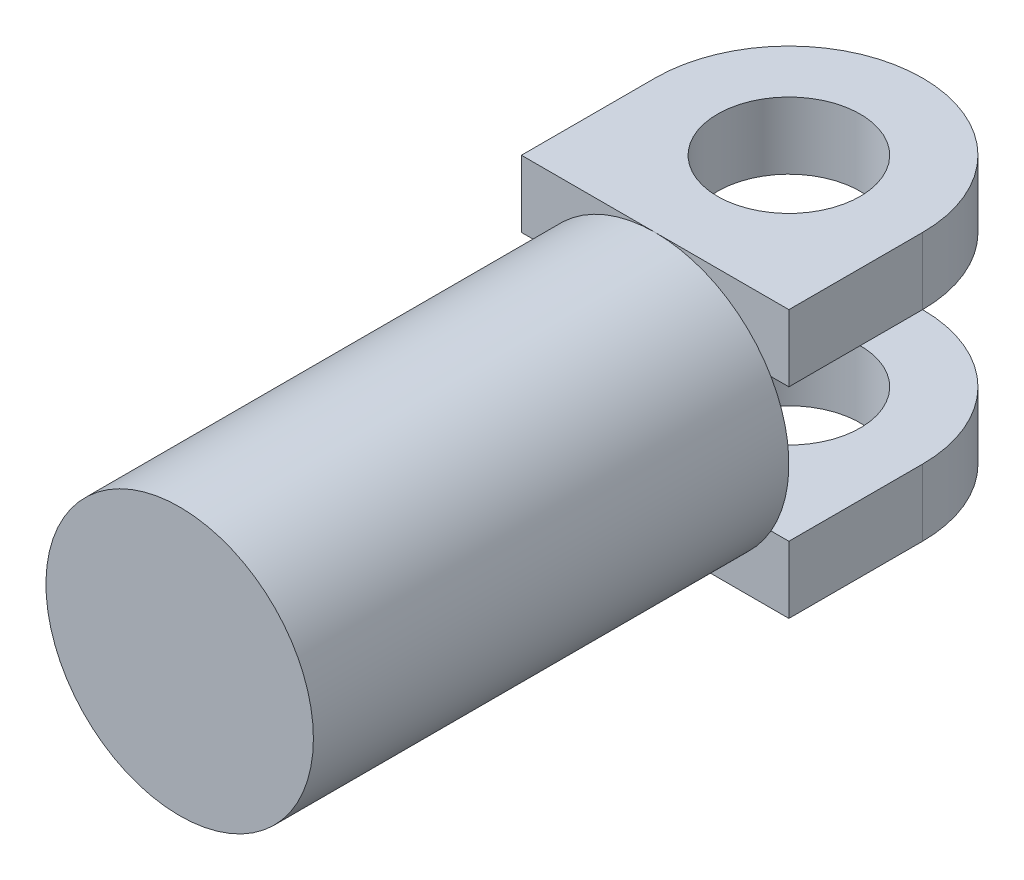
SolidWorks part; units mm, degrees
ref_plane "Front Plane" through (0, 0, 0) normal (0, 0, 1) x (1, 0, 0)
ref_plane "Top Plane" through (0, 0, 0) normal (0, 1, 0) x (1, 0, 0)
ref_plane "Right Plane" through (0, 0, 0) normal (1, 0, 0) x (0, 0, -1)
sketch "Sketch1" plane through (0, 0, 0) normal (0, 0, 1) x (1, 0, 0)
  circle A0 centre (0, 0) radius 90
  dimension "D1" = 180
extrude "Boss-Extrude1" add sketch "Sketch1" along normal blind 320
sketch "Sketch2" plane through (0, 0, 0) normal (0, 1, 0) x (1, 0, 0)
  line L0 (0, 0) -> (0, 90)
  line L1 (-90, 90) -> (-90, -6.6263)
  line L2 (90, 0) -> (-90, 0) construction
  line L3 (90, 0) -> (-90, 0)
  line L4 (90, 0) -> (90, 90)
  circle A0 centre (0, 90) radius 90
  circle A1 centre (0, 90) radius 48
  dimension "D2" = 96
  dimension "D1" = 90
extrude "Boss-Extrude2" add sketch "Sketch2" along normal blind 90 and the other way blind 90 contours A1 A0 | A0 L1 L3 | A0 L3 L4 region at (69.8969, 0, -20.1031) region at (-69.8969, 0, -20.1031) region at (-61.8396, 0, -28.1604)
sketch "Sketch3" plane through (-90, 0, 0) normal (-1, 0, 0) x (0, 0, 1)
  line L0 (0, -90) -> (0, 0) construction
  line L1 (0, -45) -> (-213.4354, -45)
  line L2 (0, -45) -> (0, 45)
  line L3 (0, 45) -> (-213.4354, 45)
  line L4 (-213.4354, -45) -> (-213.4354, 45)
  line L5 (-90, 90) -> (0, 90) construction
  line L6 (-90, -90) -> (0, -90) construction
  dimension "D1" = 45
  dimension "D2" = 45
extrude "Cut-Extrude1" cut sketch "Sketch3" against normal blind 663
